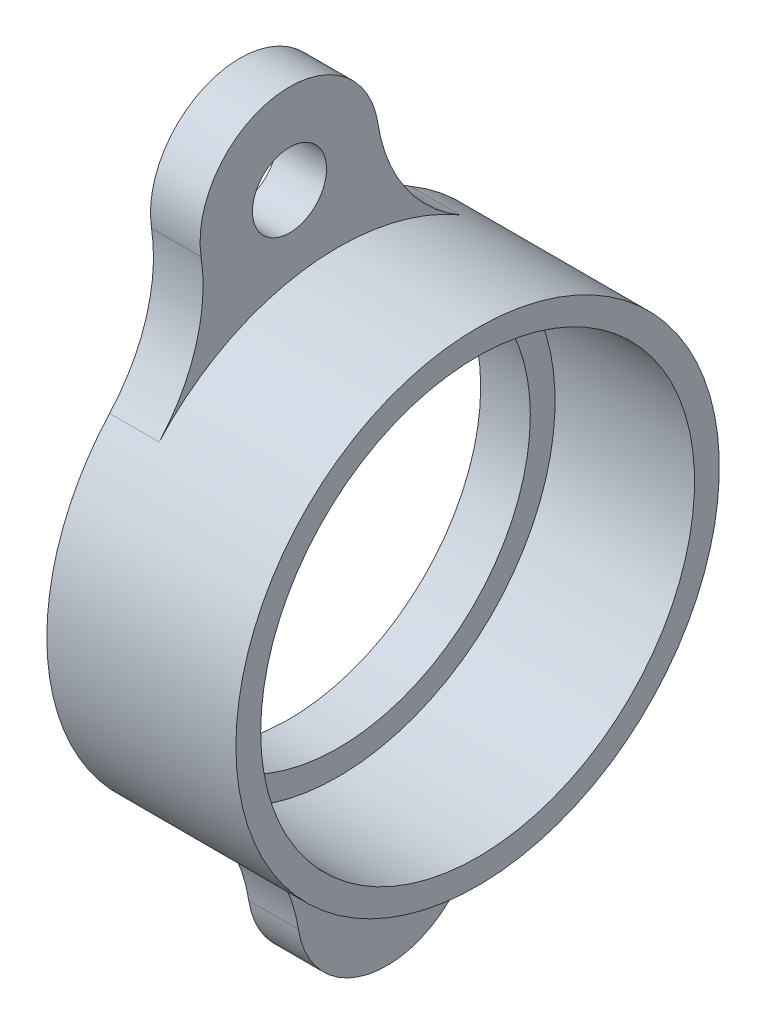
SolidWorks part; units mm, degrees
material "6061-T6 (SS)"
ref_plane "Front Plane" through (0, 0, 0) normal (0, 0, 1) x (1, 0, 0)
ref_plane "Top Plane" through (0, 0, 0) normal (0, 1, 0) x (1, 0, 0)
ref_plane "Right Plane" through (0, 0, 0) normal (1, 0, 0) x (0, 0, -1)
sketch "Sketch1" plane through (0, 0, 0) normal (0, 0, 1) x (1, 0, 0)
  line L0 (23.3719, 12.3825) -> (30.5156, 12.3825)
  line L1 (30.5156, 12.3825) -> (30.5156, 11.1125)
  line L2 (30.5156, 11.1125) -> (23.3719, 11.1125)
  line L4 (23.3719, 11.1125) -> (23.3719, 12.3825)
  line L5 (0, 0) -> (40.0174, 0) construction
  point P2 (43.3616, 7.6951)
  point P5 (32.6642, 12.3825)
  dimension "D1" = 22.225
  dimension "D2" = 7.1437
revolve "Revolve1" add sketch "Sketch1" angle 360 about L5
sketch "Sketch2" plane through (23.3719, 0, 0) normal (1, 0, 0) x (0, 0, -1)
  line L0 (0, 0) -> (-2.4917, 16.1603) construction
  line L1 (-7.0209, 15.4619) -> (2.0375, 16.8586) construction
  line L2 (-10.9827, -1.6934) -> (10.9827, 1.6934) construction
  line L4 (-4.1515, 11.8887) -> (0.3777, 12.5871) construction
  line L5 (0.3777, 12.5871) -> (2.0375, 16.8586) construction
  line L6 (2.0375, 16.8586) -> (-0.8319, 20.4319) construction
  line L7 (-0.8319, 20.4319) -> (-5.3611, 19.7335) construction
  line L8 (-5.3611, 19.7335) -> (-7.0209, 15.4619) construction
  line L9 (-7.0209, 15.4619) -> (-4.1515, 11.8887) construction
  arc A0 (-9.1674, 8.3237) -> (-6.2344, -10.6985) centre (0, 0) ccw
  circle A1 centre (0, 0) radius 12.3825 construction
  arc A7 (2.0375, 16.8586) -> (-7.0209, 15.4619) centre (-2.4917, 16.1603) ccw
  arc A8 (-9.1674, 8.3237) -> (-7.0209, 15.4619) centre (-15.5764, 14.1428) ccw
  arc A9 (2.0375, 16.8586) -> (6.2344, 10.6985) centre (10.5929, 18.1778) ccw
  circle A10 centre (0, 0) radius 9.8425
  circle A11 centre (0, 0) radius 11.1125 construction
  arc A16 (9.1674, -8.3237) -> (6.2344, 10.6985) centre (0, 0) ccw
  circle A17 centre (-2.4917, 16.1603) radius 3.9688 construction
  circle A18 centre (-2.4917, 16.1603) radius 2.1526 construction
  circle A19 centre (-2.4917, 16.1603) radius 2.1526 construction
  circle A20 centre (0, 0) radius 11.1125 construction
  arc A21 (7.0209, -15.4619) -> (9.1674, -8.3237) centre (15.5764, -14.1428) cw
  arc A22 (-6.2344, -10.6985) -> (-2.0375, -16.8586) centre (-10.5929, -18.1778) cw
  arc A23 (7.0209, -15.4619) -> (-2.0375, -16.8586) centre (2.4917, -16.1603) cw
  point P29 (-7.0209, -10.6985)
  point P30 (9.45, -8.0015)
  dimension "D1" = 1.27
  dimension "D3" = 7.9375
extrude "Boss-Extrude1" add sketch "Sketch2" against normal blind 2.54
hole_wizard "#6 Clearance Hole1" positions "Sketch3" profile "Sketch5" hole size "#6" standard "ANSI Inch" end condition up to next
sketch "Sketch3" plane through (20.8319, 0, 0) normal (-1, 0, 0) x (0, 0, 1)
  arc A0 (-7.0209, -15.4619) -> (2.0375, -16.8586) centre (-2.4917, -16.1603) ccw construction
  point P0 (2.4917, 16.1603)
  point P3 (-2.4917, -16.1603)
  point P6 (0, 0)
sketch "Sketch5" plane through (20.8319, 16.1603, 2.4917) normal (0, 1, 0) x (0, 0, 1)
  line L0 (0, 0) -> (0, 2.54)
  line L1 (0, 2.54) -> (1.8986, 2.54)
  line L2 (1.8986, 2.54) -> (1.8986, 0)
  line L5 (1.8986, 0) -> (0, 0)
  line L11 (0, -6.35) -> (0, 107.95) construction
  dimension "Thru Hole Dia." = 3.7973
  dimension "Thru Hole Depth" = 2.54
